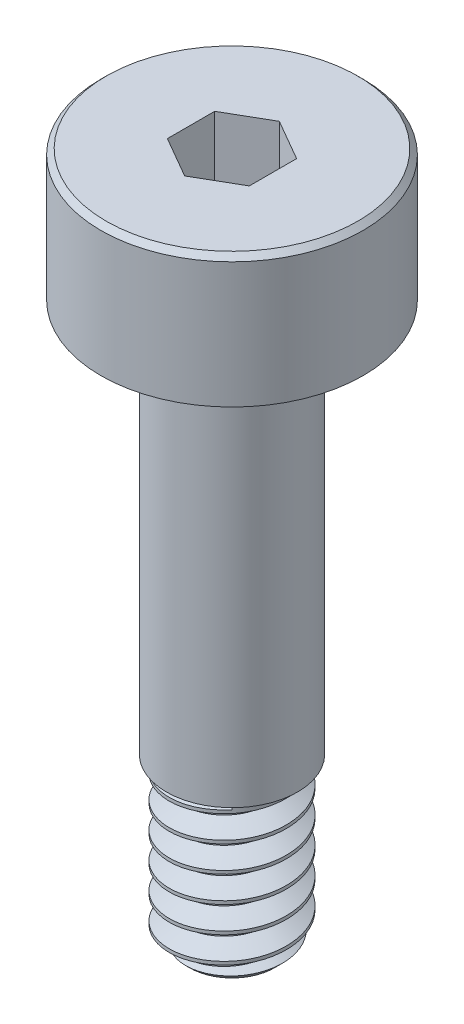
SolidWorks part; units mm, degrees
material "Alloy Steel (SS)"
ref_plane "Front" through (0, 0, 0) normal (0, 0, 1) x (1, 0, 0)
ref_plane "Top" through (0, 0, 0) normal (0, 1, 0) x (1, 0, 0)
ref_plane "Right" through (0, 0, 0) normal (1, 0, 0) x (0, 0, -1)
sketch "Sketch1" plane through (0, 0, 0) normal (0, 1, 0) x (1, 0, 0)
  circle A0 centre (0, 0) radius 3.175
  point P3 (0, -3.175)
  dimension "Head Dia" = 6.35
extrude "Extrude1" add sketch "Sketch1" along normal blind 3.175
sketch "Sketch2" plane through (0, 3.175, 0) normal (0, 1, 0) x (-1, 0, 0)
  line L1 (0, -1.1457) -> (0.9922, -0.5728)
  line L2 (0.9922, -0.5728) -> (0.9922, 0.5728)
  line L3 (0.9922, 0.5728) -> (0, 1.1457)
  line L4 (0, 1.1457) -> (-0.9922, 0.5728)
  line L5 (-0.9922, 0.5728) -> (-0.9922, -0.5728)
  line L6 (-0.9922, -0.5728) -> (0, -1.1457)
  circle A0 centre (0, 0) radius 0.9922 construction
  circle A1 centre (0, 0) radius 3.175 construction
  dimension "Hex Key" = 1.9844
extrude "Cut-Extrude1" cut sketch "Sketch2" against normal blind 1.5875
sketch "Sketch4" plane through (0, 0, 0) normal (0, -1, 0) x (1, 0, 0)
  circle A0 centre (0, 0) radius 1.5875
  circle A1 centre (0, 0) radius 3.175 construction
  dimension "Shoulder Dia" = 3.175
extrude "Extrude2" add sketch "Sketch4" along normal blind 9.525
sketch "Sketch5" plane through (0, -9.525, 0) normal (0, -1, 0) x (1, 0, 0)
  circle A0 centre (0, 0) radius 1.4224
  circle A1 centre (0, 0) radius 1.5875 construction
  dimension "Thread Dia" = 2.8448
extrude "Extrude3" add sketch "Sketch5" along normal blind 3.9688
chamfer "Chamfer1" distance 0.3969 angle 45 1 edges at (0, -13.4938, -1.4224)
sketch "Sketch12" plane through (0, -13.4938, 0) normal (0, -1, 0) x (1, 0, 0)
  circle A0 centre (0, 0) radius 1.4224
  circle A1 centre (0, 0) radius 1.4224 construction
curve "Helix/Spiral1" pitch 0.635 height 3.9688 turns 6.25 parameters "Thread Pitch "=0.635
sketch "Sketch13" plane through (0, 0, 0) normal (0, 0, 1) x (1, 0, 0)
  line L0 (1.4224, -13.4938) -> (1.4224, -14.0494)
  line L1 (1.4224, -14.0494) -> (1.01, -13.8112)
  line L2 (1.01, -13.8112) -> (1.01, -13.7319)
  line L3 (1.01, -13.7319) -> (1.4224, -13.4938)
  line L4 (1.4224, -13.7716) -> (1.01, -13.7716) construction
  line L5 (1.4224, -13.0969) -> (1.4224, -9.525) construction
  line L6 (1.2162, -13.6128) -> (1.2162, -13.9303) construction
  line L7 (-1.0255, -13.4938) -> (1.0255, -13.4938) construction
  dimension "D1" = 60
  dimension "D2" = 0.0794
  dimension "D3" = 0.3175
sweep "Cut-Sweep1" cut profiles "Sketch13" path "Helix/Spiral1"
sketch "Sketch10" plane through (0, 3.175, 0) normal (0, 1, 0) x (-1, 0, 0)
  line L0 (0, 0) -> (-3.0455, 0) construction
  line L1 (0, 0) -> (-11.9081, -0.5199) construction
  line L2 (-3.172, -0.1385) -> (-3.2185, -0.1405)
  line L3 (-3.172, -0.1385) -> (-3.054, -0.0205)
  line L4 (0, 0) -> (-11.9081, 0.5199) construction
  line L5 (-3.054, 0.0205) -> (-3.172, 0.1385)
  line L6 (-3.2185, -0.1405) -> (-3.2185, 0.1405)
  line L7 (-3.2185, 0.1405) -> (-3.172, 0.1385)
  circle A0 centre (0, 0) radius 3.175 construction
  arc A2 (-3.054, -0.0205) -> (-3.054, 0.0205) centre (-3.0745, 0) ccw
  point P3 (-3.175, 0)
  dimension "D4" = 0.029
  dimension "D1" = 90
  dimension "D2" = 5
  dimension "D3" = 0.0465
sketch "Sketch11" plane through (0, 0, 0) normal (0, 0, 1) x (1, 0, 0)
  line L0 (3.175, 3.0455) -> (3.0455, 3.175)
  line L1 (3.0455, 3.175) -> (3.175, 3.175)
  line L2 (3.175, 3.175) -> (3.175, 3.0455)
  line L3 (3.054, 3.175) -> (3.0455, 3.175) construction
  line L6 (0, 14.5442) -> (0, -6.8202) construction
revolve "Cut-Revolve7" cut sketch "Sketch11" angle 360 about L6
sketch "Sketch14" plane through (0, 3.175, 0) normal (0, 1, 0) x (1, 0, 0)
  circle A0 centre (0, 0) radius 3.175
  circle A2 centre (0, 0) radius 3.175 construction
sketch "Sketch15" plane through (0, 0, 0) normal (1, 0, 0) x (0, 0, -1)
  line L0 (-1.4224, -9.525) -> (-1.4224, -13.4938) construction
  line L1 (1.4224, -13.4938) -> (1.4224, -9.525) construction
  line L2 (-1.5875, -9.525) -> (1.5875, -9.525) construction
equation "\"D1@Cut-Extrude1\"=\"Head Ht@Extrude1\"/2"
equation "\"D1@Chamfer1\" = \"Thread Length@Extrude3\" * .1"
equation "\"D3@Helix/Spiral1\" = \"Thread Length@Extrude3\""
equation "\"D2@Sketch13\" = \"Thread Pitch @Helix/Spiral1\" * .125"
equation "\"D3@Sketch13\" = \"Thread Pitch @Helix/Spiral1\" * .5"
equation "\"D3@Sketch10\" = \"Head Dia@Sketch1\" * .0073205143"
equation "\"D4@Sketch10\" = \"Head Dia@Sketch1\" * .0045714286"
